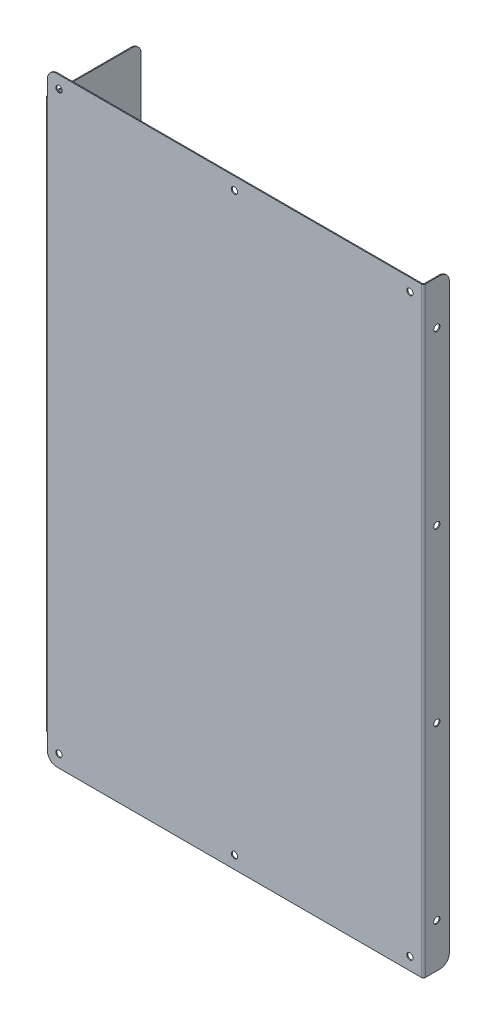
SolidWorks part; units mm, degrees
note: The reader was unsure of these and kept them because the rebuilt part matched: bend radius of "BaseBend2", "BaseBend3".
ref_plane "Front Plane" through (0, 0, 0) normal (0, 0, 1) x (1, 0, 0)
ref_plane "Top Plane" through (0, 0, 0) normal (0, 1, 0) x (1, 0, 0)
ref_plane "Right Plane" through (0, 0, 0) normal (1, 0, 0) x (0, 0, -1)
sketch "Sketch1" plane through (0, 0, 0) normal (0, 1, 0) x (1, 0, 0)
  line L0 (300.5, 40) -> (300.5, 0)
  line L1 (300.5, 0) -> (-300.5, 0)
  line L2 (-300.5, 0) -> (-300.5, 150)
  dimension "D1" = 601
  dimension "D2" = 40
  dimension "D3" = 150
base flange "Base-Flange1" sketch "Sketch1" end condition mid plane depth 960 reverse direction no thickness 1.5 reverse thickness direction yes bend radius 1.5
bend "BaseBend2" bend radius 1.5 bend angle 90 parameters "D5"=2
bend "BaseBend3" bend radius 1.5 bend angle 90 parameters "D5"=3
sketch "Sketch6" plane through (-302, 0, 0) normal (-1, 0, 0) x (0, 0, 1)
  line L0 (-1.5, 480) -> (-150, 480) construction
  line L1 (-158.5, 480) -> (11.5, 480)
  line L2 (-158.5, 480) -> (-158.5, 439)
  line L3 (-158.5, 439) -> (11.5, 439)
  line L4 (11.5, 480) -> (11.5, 439)
  line L6 (1.5, 480) -> (1.5, -480) construction
  dimension "D1" = 41
  dimension "D2" = 170
  dimension "D3" = 10
extrude "Cut-Extrude1" cut sketch "Sketch6" against normal up to vertex (3 mm away) and the other way through all normal cut yes up to point (-299, 480, 1.5)
mirror "Mirror1" about plane through (0, 0, 0) normal (0, 1, 0) of "Cut-Extrude1"
hole_wizard "M5 Clearance Hole1" positions "Sketch7" profile "Sketch8" hole size "M5" standard "ISO" end condition through all
sketch "Sketch7" plane through (-302, 0, 0) normal (-1, 0, 0) x (0, 0, 1)
  circle A0 centre (-75.75, -379) radius 2.9 construction
  circle A1 centre (-75.75, -189.5) radius 2.9 construction
  circle A2 centre (-75.75, 0) radius 2.9 construction
  circle A3 centre (-75.75, 189.5) radius 2.9 construction
  circle A4 centre (-75.75, 379) radius 2.9 construction
  circle A5 centre (-75.75, -379) radius 2.9
  circle A6 centre (-75.75, -189.5) radius 2.9
  circle A7 centre (-75.75, 0) radius 2.9
  circle A8 centre (-75.75, 189.5) radius 2.9
  circle A9 centre (-75.75, 379) radius 2.9
  point P1 (-75.75, -379)
  point P3 (-75.75, -189.5)
  point P5 (-75.75, 0)
  point P7 (-75.75, 189.5)
  point P9 (-75.75, 379)
sketch "Sketch8" plane through (-302, -379, -75.75) normal (0, 1, 0) x (0, 0, 1)
  line L0 (0, 0) -> (0, 604)
  line L1 (0, 604) -> (2.9, 604)
  line L2 (2.9, 604) -> (2.9, 0)
  line L5 (2.9, 0) -> (0, 0)
  line L11 (0, -6.35) -> (0, 107.95) construction
  dimension "Thru Hole Dia." = 5.8
  dimension "Thru Hole Depth" = 604
fillet "Fillet1" radius 15 6 edges at (-299, -480, 0.75) (-301.25, -439, -150) (-299, 480, 0.75) (-301.25, 439, -150) (301.25, -480, -40) (301.25, 480, -40)
hole_wizard "M8 Clearance Hole1" positions "Sketch9" profile "Sketch10" hole size "M8" standard "ISO"
sketch "Sketch9" plane through (0, 0, 1.5) normal (0, 0, 1) x (1, 0, 0)
  line L0 (-280.5, 460) -> (0, 460) construction
  line L1 (0, 460) -> (280.5, 460) construction
  line L3 (0, 0) -> (0, 460) construction
  line L5 (299, 480) -> (-284, 480) construction
  point P0 (-280.5, 460)
  point P2 (0, 460)
  point P4 (280.5, 460)
  dimension "D1" = 20
  dimension "D2" = 20
sketch "Sketch10" plane through (-280.5, 460, 1.5) normal (1, 0, 0) x (0, -1, 0)
  line L0 (0, 0) -> (0, 12)
  line L1 (0, 12) -> (5, 8.9957)
  line L2 (5, 8.9957) -> (5, 0)
  line L5 (5, 0) -> (0, 0)
  line L10 (0, 12) -> (-5, 8.9957) construction
  line L11 (0, -6.35) -> (0, 107.95) construction
  dimension "Hole Dia." = 10
  dimension "Hole Depth" = 12
  dimension "Drill Angle" = 118
mirror "Mirror2" about plane through (0, 0, 0) normal (0, 1, 0) of "M8 Clearance Hole1"
hole_wizard "M8 Clearance Hole2" positions "Sketch11" profile "Sketch12" hole size "M8" standard "ISO"
sketch "Sketch11" plane through (302, 0, 0) normal (1, 0, 0) x (0, 0, -1)
  line L0 (20, 410) -> (20, 136.6667) construction
  line L1 (20, 136.6667) -> (20, -136.6667) construction
  line L2 (20, -136.6667) -> (20, -410) construction
  line L3 (20, -410) -> (20, -480) construction
  line L4 (25, -480) -> (1.5, -480) construction
  line L6 (20, 410) -> (20, 480) construction
  line L7 (25, 480) -> (1.5, 480) construction
  point P0 (20, 410)
  point P2 (20, 136.6667)
  point P4 (20, -136.6667)
  point P6 (20, -410)
  dimension "D1" = 70
  dimension "D2" = 20
sketch "Sketch12" plane through (302, 410, -20) normal (0, 1, 0) x (0, 0, -1)
  line L0 (0, 0) -> (0, 12)
  line L1 (0, 12) -> (5, 8.9957)
  line L2 (5, 8.9957) -> (5, 0)
  line L5 (5, 0) -> (0, 0)
  line L10 (0, 12) -> (-5, 8.9957) construction
  line L11 (0, -6.35) -> (0, 107.95) construction
  dimension "Hole Dia." = 10
  dimension "Hole Depth" = 12
  dimension "Drill Angle" = 118
hole_wizard "M8 Clearance Hole3" positions "Sketch13" profile "Sketch14" hole size "M8" standard "ISO"
sketch "Sketch13" plane through (-302, 0, 0) normal (-1, 0, 0) x (0, 0, 1)
  circle A0 centre (-20, 369) radius 5 construction
  circle A1 centre (-20, 0) radius 5 construction
  circle A2 centre (-20, -369) radius 5 construction
  point P0 (-20, 369)
  point P2 (-20, 0)
  point P4 (-20, -369)
sketch "Sketch14" plane through (-302, 369, -20) normal (0, 1, 0) x (0, 0, 1)
  line L0 (0, 0) -> (0, 12)
  line L1 (0, 12) -> (5, 8.9957)
  line L2 (5, 8.9957) -> (5, 0)
  line L5 (5, 0) -> (0, 0)
  line L10 (0, 12) -> (-5, 8.9957) construction
  line L11 (0, -6.35) -> (0, 107.95) construction
  dimension "Hole Dia." = 10
  dimension "Hole Depth" = 12
  dimension "Drill Angle" = 118
sketch "Bend-Lines1" [suppressed] plane through (0, 0, 0) normal (0, 1, 0) x (1, 0, 0)
sketch "Bounding-Box1" [suppressed] plane through (0, 0, 0) normal (0, 1, 0) x (1, 0, 0)
sheet metal parameters "Sheet-Metal1" thickness 1.5 parameters "D1"=1.5
flat pattern "Flat-Pattern1" [suppressed]
sketch "Bend-Lines2" plane through (0, 0, 1.5) normal (0, 0, 1) x (1, 0, 0)
  line L0 (300.7671, 480) -> (300.7671, -480) construction
  line L1 (-300.7671, -480) -> (-300.7671, 480) construction
  line L2 (-449.8014, -480) -> (-449.8014, 480) construction
  line L3 (300.7671, 480) -> (300.7671, -480) construction
  line L4 (-300.7671, -480) -> (-300.7671, 480) construction
  line L5 (-449.8014, -480) -> (-449.8014, 480) construction
sketch3d "Bounding-Box2" [suppressed]
  line L0 (40.5343, 0, 0) -> (40.5343, -960, 0) construction
  line L1 (-769.0686, 0, 0) -> (-769.0686, -960, 0) construction
  line L2 (40.5343, 0, 0) -> (-769.0686, 0, 0) construction
  line L3 (40.5343, -960, 0) -> (-769.0686, -960, 0) construction
bend of the flat pattern "Flatten-<BaseBend2>1"
bend of the flat pattern "Flatten-<BaseBend3>1"
sheet metal parameters "Sheet-Metal2" thickness 1.5 parameters "D1"=1.5
flat pattern "Flat-Pattern1"
sketch "Bend-Lines2" plane through (0, 0, 1.5) normal (0, 0, 1) x (1, 0, 0)
  line L0 (300.7671, 480) -> (300.7671, -480) construction
  line L1 (-300.7671, -480) -> (-300.7671, 439) construction
  line L2 (-449.8014, -480) -> (-449.8014, 439) construction
  line L3 (300.7671, 480) -> (300.7671, -480) construction
  line L4 (-300.7671, -480) -> (-300.7671, 439) construction
  line L5 (-449.8014, -480) -> (-449.8014, 439) construction
sketch3d "Bounding-Box2" [suppressed]
  line L0 (40.5343, 0, 0) -> (40.5343, -960, 0) construction
  line L1 (-769.0686, 0, 0) -> (-769.0686, -960, 0) construction
  line L2 (40.5343, 0, 0) -> (-769.0686, 0, 0) construction
  line L3 (40.5343, -960, 0) -> (-769.0686, -960, 0) construction
bend of the flat pattern "Flatten-<BaseBend2>1"
bend of the flat pattern "Flatten-<BaseBend3>1"
sheet metal parameters "Sheet-Metal3" thickness 1.5 parameters "D1"=1.5
flat pattern "Flat-Pattern1"
sketch "Bend-Lines2" plane through (0, 0, 1.5) normal (0, 0, 1) x (1, 0, 0)
  line L0 (300.7671, 480) -> (300.7671, -480) construction
  line L1 (-300.7671, -439) -> (-300.7671, 439) construction
  line L2 (-449.8014, -439) -> (-449.8014, 439) construction
  line L3 (300.7671, 480) -> (300.7671, -480) construction
  line L4 (-300.7671, -439) -> (-300.7671, 439) construction
  line L5 (-449.8014, -439) -> (-449.8014, 439) construction
sketch3d "Bounding-Box2" [suppressed]
  line L0 (40.5343, 0, 0) -> (40.5343, -960, 0) construction
  line L1 (-769.0686, 0, 0) -> (-769.0686, -960, 0) construction
  line L2 (40.5343, 0, 0) -> (-769.0686, 0, 0) construction
  line L3 (40.5343, -960, 0) -> (-769.0686, -960, 0) construction
bend of the flat pattern "Flatten-<BaseBend2>1"
bend of the flat pattern "Flatten-<BaseBend3>1"
sheet metal parameters "Sheet-Metal4" thickness 1.5 parameters "D1"=1.5
flat pattern "Flat-Pattern1"
sketch "Bend-Lines2" plane through (0, 0, 1.5) normal (0, 0, 1) x (1, 0, 0)
  line L0 (300.7671, 480) -> (300.7671, -480) construction
  line L1 (-300.7671, -439) -> (-300.7671, 439) construction
  line L3 (300.7671, 480) -> (300.7671, -480) construction
  line L4 (-300.7671, -439) -> (-300.7671, 439) construction
sketch3d "Bounding-Box2" [suppressed]
  line L0 (40.5343, -960, 0) -> (40.5343, 0, 0) construction
  line L1 (-751.5343, -960, 0) -> (-751.5343, 0, 0) construction
  line L2 (40.5343, -960, 0) -> (-751.5343, -960, 0) construction
  line L3 (40.5343, 0, 0) -> (-751.5343, 0, 0) construction
bend of the flat pattern "Flatten-<BaseBend2>1"
bend of the flat pattern "Flatten-<BaseBend3>1"
sheet metal parameters "Sheet-Metal5" thickness 1.5 parameters "D1"=1.5
flat pattern "Flat-Pattern1"
sketch "Bend-Lines2" plane through (0, 0, 1.5) normal (0, 0, 1) x (1, 0, 0)
  line L0 (300.7671, 480) -> (300.7671, -480) construction
  line L1 (-300.7671, -439) -> (-300.7671, 439) construction
  line L3 (300.7671, 480) -> (300.7671, -480) construction
  line L4 (-300.7671, -439) -> (-300.7671, 439) construction
sketch3d "Bounding-Box2" [suppressed]
  line L0 (40.5343, -960, 0) -> (40.5343, 0, 0) construction
  line L1 (-751.5343, -960, 0) -> (-751.5343, 0, 0) construction
  line L2 (40.5343, -960, 0) -> (-751.5343, -960, 0) construction
  line L3 (40.5343, 0, 0) -> (-751.5343, 0, 0) construction
bend of the flat pattern "Flatten-<BaseBend2>1"
bend of the flat pattern "Flatten-<BaseBend3>1"
sheet metal parameters "Sheet-Metal6" thickness 1.5 parameters "D1"=1.5
flat pattern "Flat-Pattern1"
sketch "Bend-Lines2" plane through (0, 0, 1.5) normal (0, 0, 1) x (1, 0, 0)
  line L0 (300.7671, 480) -> (300.7671, -480) construction
  line L1 (-300.7671, -439) -> (-300.7671, 439) construction
  line L3 (300.7671, 480) -> (300.7671, -480) construction
  line L4 (-300.7671, -439) -> (-300.7671, 439) construction
sketch3d "Bounding-Box2" [suppressed]
  line L0 (40.5343, -960, 0) -> (40.5343, 0, 0) construction
  line L1 (-751.5343, -960, 0) -> (-751.5343, 0, 0) construction
  line L2 (40.5343, -960, 0) -> (-751.5343, -960, 0) construction
  line L3 (40.5343, 0, 0) -> (-751.5343, 0, 0) construction
bend of the flat pattern "Flatten-<BaseBend2>1"
bend of the flat pattern "Flatten-<BaseBend3>1"
sheet metal parameters "Sheet-Metal7" thickness 1.5 parameters "D1"=1.5
flat pattern "Flat-Pattern1"
sketch "Bend-Lines2" plane through (0, 0, 1.5) normal (0, 0, 1) x (1, 0, 0)
  line L0 (300.7671, 480) -> (300.7671, -480) construction
  line L1 (-300.7671, -439) -> (-300.7671, 439) construction
  line L3 (300.7671, 480) -> (300.7671, -480) construction
  line L4 (-300.7671, -439) -> (-300.7671, 439) construction
sketch3d "Bounding-Box2" [suppressed]
  line L0 (40.5343, -960, 0) -> (40.5343, 0, 0) construction
  line L1 (-751.5343, -960, 0) -> (-751.5343, 0, 0) construction
  line L2 (40.5343, -960, 0) -> (-751.5343, -960, 0) construction
  line L3 (40.5343, 0, 0) -> (-751.5343, 0, 0) construction
bend of the flat pattern "Flatten-<BaseBend2>1"
bend of the flat pattern "Flatten-<BaseBend3>1"
sheet metal parameters "Sheet-Metal8" thickness 1.5 parameters "D1"=1.5
flat pattern "Flat-Pattern1"
sketch "Bend-Lines2" plane through (0, 0, 1.5) normal (0, 0, 1) x (1, 0, 0)
  line L0 (300.7671, 480) -> (300.7671, -480) construction
  line L1 (-300.7671, -439) -> (-300.7671, 439) construction
  line L3 (300.7671, 480) -> (300.7671, -480) construction
  line L4 (-300.7671, -439) -> (-300.7671, 439) construction
sketch3d "Bounding-Box2" [suppressed]
  line L0 (40.5343, -960, 0) -> (40.5343, 0, 0) construction
  line L1 (-751.5343, -960, 0) -> (-751.5343, 0, 0) construction
  line L2 (40.5343, -960, 0) -> (-751.5343, -960, 0) construction
  line L3 (40.5343, 0, 0) -> (-751.5343, 0, 0) construction
bend of the flat pattern "Flatten-<BaseBend2>1"
bend of the flat pattern "Flatten-<BaseBend3>1"
